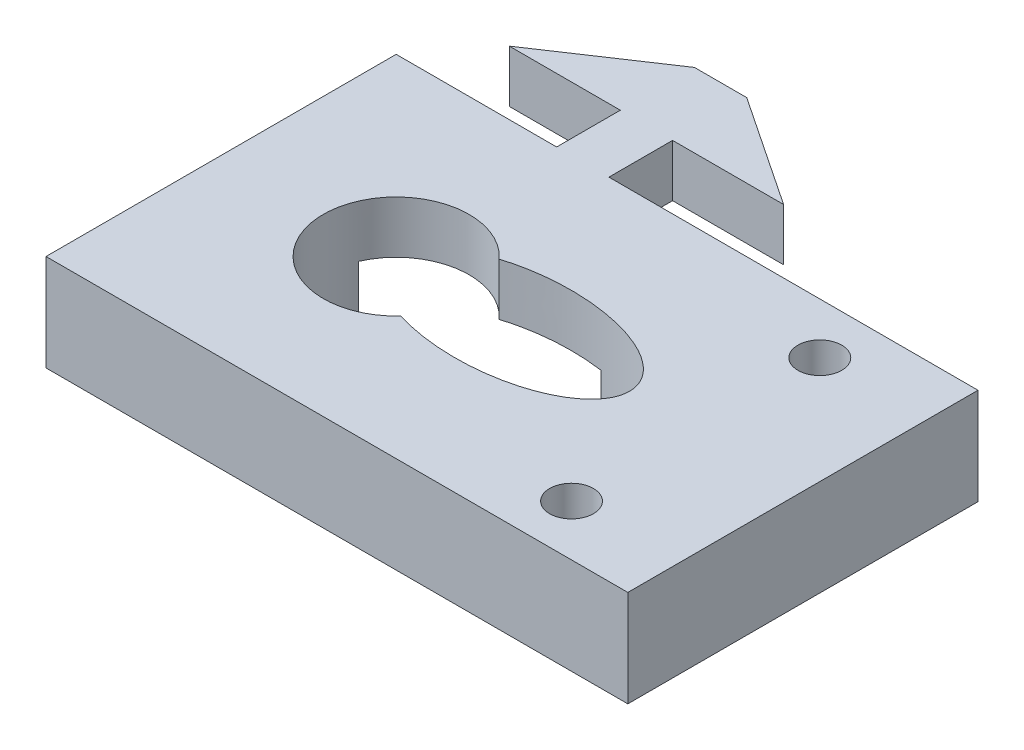
SolidWorks part; units mm, degrees
ref_plane "Front" through (0, 0, 0) normal (0, 0, 1) x (1, 0, 0)
ref_plane "Top" through (0, 0, 0) normal (0, 1, 0) x (1, 0, 0)
ref_plane "Right" through (0, 0, 0) normal (1, 0, 0) x (0, 0, -1)
sketch "Sketch1" plane through (0, 0, 0) normal (0, 1, 0) x (1, 0, 0)
  line L0 (-1.7907, 2.1825) -> (-9.398, 2.1825)
  line L2 (-1.7907, -2.1825) -> (-1.7907, 2.1825)
  line L4 (1.7907, -2.1825) -> (1.7907, 2.1825)
  line L7 (-9.398, 2.1825) -> (-1.7907, 7.2625)
  line L8 (-1.7907, 7.2625) -> (1.7907, 7.2625)
  line L9 (1.7907, 7.2625) -> (9.398, 2.1825)
  line L10 (9.398, 2.1825) -> (1.7907, 2.1825)
  line L11 (1.7907, -2.1825) -> (27.088, -2.1825)
  line L12 (-1.7907, -2.1825) -> (-12.79, -2.1825)
  line L13 (-12.79, -2.1825) -> (-12.79, -26.1825)
  line L14 (-12.79, -26.1825) -> (27.088, -26.1825)
  line L15 (27.088, -26.1825) -> (27.088, -2.1825)
  line L16 (27.088, -2.1825) -> (1.7907, -2.1825)
  point P0 (0, 0)
  point P17 (0, 7.2625)
  point P24 (1.7907, 0)
  dimension "D1" = 18.796
  dimension "D2" = 3.5814
  dimension "D3" = 39.878
  dimension "D4" = 24
  dimension "D5" = 5.08
  dimension "D6" = 12.79
  dimension "D7" = 4.365
extrude "Boss-Extrude1" add sketch "Sketch1" along normal blind 3.5814 contours L14 L15 L11 L4 L10 L9 L8 L7 L0 L2 L12 L13 region at (6.6458, 0, 12.9552)
ref_plane "Plane1" through (0, 1.7907, 0) normal (0, 1, 0) x (1, 0, 0)
sketch "Sketch7" plane through (0, 0, 0) normal (0, 1, 0) x (1, 0, 0)
  line L1 (-12.79, -2.1825) -> (27.088, -2.1825)
  line L2 (-12.79, -2.1825) -> (-12.79, -26.1825)
  line L3 (-12.79, -26.1825) -> (27.088, -26.1825)
  line L4 (27.088, -2.1825) -> (27.088, -26.1825)
extrude "Boss-Extrude2" add sketch "Sketch7" along normal blind 3.035 and the other way blind 3.035
sketch "Sketch5" plane through (0, 3.5814, 0) normal (0, 1, 0) x (1, 0, 0)
  line L0 (-12.79, -2.1825) -> (-12.79, -26.1825) construction
  line L1 (-12.79, -14.1825) -> (27.088, -14.1825) construction
  line L2 (27.088, -26.1825) -> (27.088, -2.1825) construction
  circle A0 centre (-0.79, -14.1825) radius 5
  circle A1 centre (19.738, -22.6915) radius 1.5
  circle A2 centre (19.738, -5.6735) radius 1.5
  ellipse E0 centre (7.21, -14.1825) end of major axis (-0.79, -14.1825) minor radius 4
  point P5 (-12.79, -14.1825)
  dimension "D2" = 10
  dimension "D6" = 3
  dimension "D1" = 12
  dimension "D3" = 8
  dimension "D4" = 16
  dimension "D5" = 17.018
  dimension "D7" = 7.35
extrude "Cut-Extrude3" cut sketch "Sketch5" against normal through all both and the other way through all contours A0 L1 E0 | E0 L1 A0 | A0 L1 E0 | L1 A0 E0 | L1 E0 A0 | L1 A0 E0 | A1 | A2 region at (1.9147, 3.5814, 12.8743) region at (-1.952, 3.5814, 16.6542) region at (1.9147, 3.5814, 15.4907) region at (-1.952, 3.5814, 11.7108) region at (8.8346, 3.5814, 12.3654) region at (8.8346, 3.5814, 15.9996) region at (19.738, 3.5814, 22.6915)
ref_plane "Plane2" through (0, 0, -17.2625) normal (0, 0, -1) x (-1, 0, 0)
sketch "Sketch8" plane through (0, 0, 2.1825) normal (0, 0, -1) x (-1, 0, 0)
  line L0 (-27.088, -3.035) -> (12.79, -3.035) construction
  line L1 (-9.398, 0) -> (9.398, 0)
  line L2 (-9.398, 0) -> (-9.398, -3.035)
  line L3 (-9.398, -3.035) -> (9.398, -3.035)
  line L4 (9.398, 0) -> (9.398, -3.035)
  line L5 (-9.398, 3.5814) -> (-9.398, 0) construction
  line L6 (9.398, 3.5814) -> (9.398, 0) construction
  line L7 (-1.7907, 0) -> (1.7907, 0) construction
extrude "Cut-Extrude4" cut sketch "Sketch8" against normal blind 10
